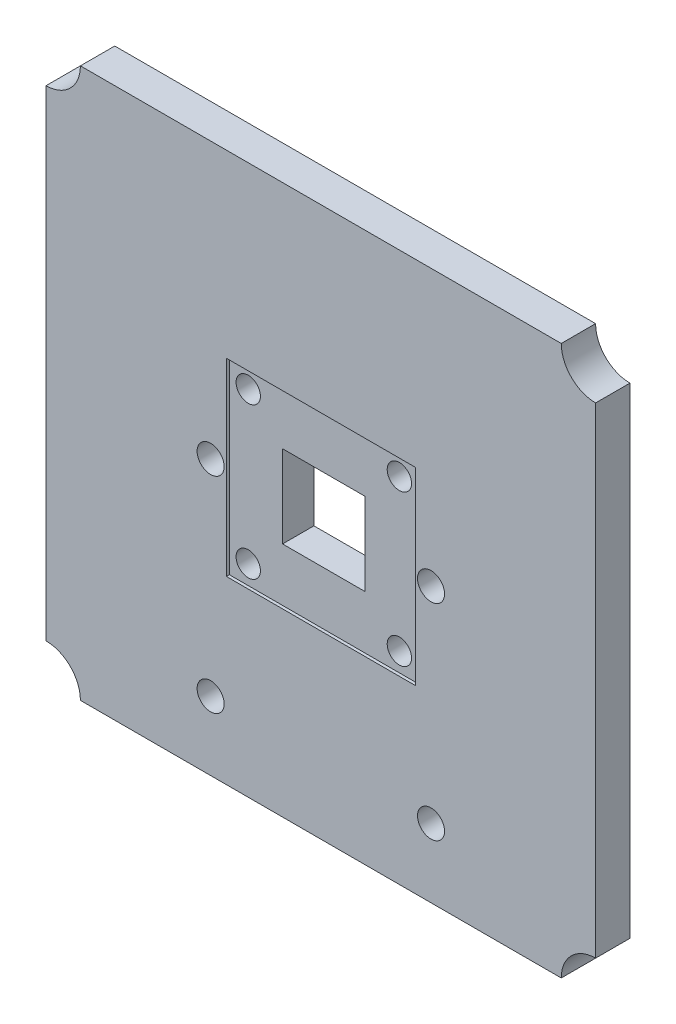
SolidWorks part; units mm, degrees
ref_plane "Front Plane" through (0, 0, 0) normal (0, 0, 1) x (1, 0, 0)
ref_plane "Top Plane" through (0, 0, 0) normal (0, 1, 0) x (1, 0, 0)
ref_plane "Right Plane" through (0, 0, 0) normal (1, 0, 0) x (0, 0, -1)
sketch "Sketch1" plane through (0, 0, 0) normal (0, 1, 0) x (1, 0, 0)
  line L1 (-57.15, 57.15) -> (57.15, 57.15)
  line L2 (-57.15, 57.15) -> (-57.15, -57.15)
  line L3 (-57.15, -57.15) -> (57.15, -57.15)
  line L4 (57.15, 57.15) -> (57.15, -57.15)
  point P4 (0, 57.15)
  point P7 (-57.15, 0)
  dimension "D1" = 114.3
  dimension "D2" = 114.3
extrude "Boss-Extrude1" add sketch "Sketch1" along normal mid plane 107.95
sketch "Sketch2" plane through (0, 53.975, 0) normal (0, 1, 0) x (1, 0, 0)
  line L1 (-50.8, 50.8) -> (50.8, 50.8)
  line L2 (-50.8, 50.8) -> (-50.8, -50.8)
  line L3 (-50.8, -50.8) -> (50.8, -50.8)
  line L4 (50.8, 50.8) -> (50.8, -50.8)
  arc A0 (-50.8, 44.45) -> (-44.45, 50.8) centre (-50.8, 50.8) ccw
  arc A1 (44.45, 50.8) -> (50.8, 44.45) centre (50.8, 50.8) ccw
  arc A2 (-50.8, -44.45) -> (-44.45, -50.8) centre (-50.8, -50.8) cw
  arc A3 (44.45, -50.8) -> (50.8, -44.45) centre (50.8, -50.8) cw
  point P4 (0, 50.8)
  point P5 (50.8, 0)
  dimension "D3" = 6.35
  dimension "D4" = 6.35
  dimension "D5" = 6.35
  dimension "D6" = 6.35
  dimension "D1" = 101.6
  dimension "D2" = 101.6
extrude "Cut-Extrude1" cut sketch "Sketch2" against normal blind 101.6 contours L3 A3 L4 A1 L1 A0 L2 A2 region at (0, 53.975, 0)
sketch "Sketch5" plane through (0, 0, -50.8) normal (0, 0, 1) x (1, 0, 0)
  line L0 (7.625, 3.185) -> (-7.625, 3.185) construction
  line L1 (-17.47, 20.655) -> (17.47, 20.655)
  line L2 (-17.47, 20.655) -> (-17.47, -14.285)
  line L3 (-17.47, -14.285) -> (17.47, -14.285)
  line L4 (17.47, 20.655) -> (17.47, -14.285)
  line L5 (-7.625, 10.81) -> (7.625, 10.81)
  line L6 (-7.625, 10.81) -> (-7.625, -4.44)
  line L7 (-7.625, -4.44) -> (7.625, -4.44)
  line L8 (7.625, 10.81) -> (7.625, -4.44)
  line L10 (-57.15, 53.975) -> (-57.15, -53.975) construction
  line L11 (0, 10.81) -> (0, -4.44) construction
  line L12 (-44.45, -47.625) -> (44.45, -47.625) construction
  point P8 (0, 10.81)
  point P9 (0, 20.655)
  point P12 (17.47, 3.185)
  point P13 (7.625, 3.185)
  dimension "D1" = 34.94
  dimension "D2" = 15.25
  dimension "D3" = 15.25
  dimension "D4" = 34.94
  dimension "D5" = 39.68
  dimension "D6" = 33.34
extrude "Cut-Extrude5" cut sketch "Sketch5" against normal blind 0.55
extrude "Cut-Extrude6" cut sketch "Sketch5<3>" against normal up to next contours L8 L5 L6 L7 | L6 L5 region at (0, 3.185, -50.8)
sketch "Sketch5<3>" plane through (0, 0, -50.8) normal (0, 0, 1) x (1, 0, 0) same geometry as "Sketch5"
sketch "Sketch13" plane through (0, 0, -57.15) normal (0, 0, -1) x (-1, 0, 0)
  line L0 (-57.15, 53.975) -> (57.15, 53.975) construction
  line L1 (-57.15, 53.975) -> (-57.15, -53.975) construction
  line L2 (57.15, 53.975) -> (57.15, -53.975) construction
  line L3 (-14.2875, 27.94) -> (-14.2875, 22.86) construction
  line L4 (14.2875, 22.86) -> (14.2875, 27.94) construction
  line L5 (13.7875, 29.177) -> (13.7875, 21.623)
  line L6 (14.7875, 29.177) -> (14.7875, 21.623)
  line L7 (11.5934, 22.7059) -> (16.9816, 28.0941)
  line L8 (11.5934, 28.0941) -> (16.9816, 22.7059)
  circle A0 centre (-14.2875, 25.4) radius 2.54
  circle A1 centre (14.2875, 25.4) radius 2.54
  circle A2 centre (14.2875, 25.4) radius 3.81
  point P19 (13.7875, 25.4)
  point P20 (14.7875, 25.4)
  dimension "D1" = 5.08
  dimension "D2" = 5.08
  dimension "D7" = 7.62
  dimension "D3" = 28.575
  dimension "D4" = 28.575
  dimension "D5" = 42.8625
  dimension "D6" = 42.8625
  dimension "D8" = 1
  dimension "D9" = 0.5
  dimension "D10" = 45
  dimension "D11" = 45
extrude "Boss-Extrude2" add sketch "Sketch13" along normal blind 1.27 contours A0
ref_plane "Plane1" through (14.2875, 25.4, -57.15) normal (0, -1, 0) x (-1, 0, 0)
sketch "Sketch14" plane through (14.2875, 25.4, -57.15) normal (0, -1, 0) x (-1, 0, 0)
  line L0 (0, 1.27) -> (0, 2.54)
  line L1 (2.54, 1.27) -> (-2.54, 1.27) construction
  line L2 (0, 2.54) -> (2.286, 2.54)
  line L3 (2.286, 2.54) -> (2.64, 1.905)
  line L4 (2.64, 1.905) -> (2.64, 1.27)
  line L5 (2.64, 1.27) -> (2.54, 1.27)
  line L6 (2.54, 0) -> (2.54, 1.27) construction
  line L7 (2.54, 1.27) -> (0, 1.27)
  dimension "D1" = 1.27
  dimension "D2" = 0.1
  dimension "D3" = 2.286
  dimension "D4" = 0.635
revolve "Revolve1" add sketch "Sketch14" angle 360 about L0
ref_plane "Plane2" through (-14.2875, 25.4, -57.15) normal (0, -1, 0) x (-1, 0, 0)
extrude "Cut-Extrude7" cut sketch "Sketch13<4>" against normal blind 2.54 contours L8 A1 L7 L6 | L6 A1 L8 | L5 A1 L6 L8 L7 | L7 A1 L6 | L6 A1 L5 L8 L7 | L7 L8 L6 | L8 L5 L7 | L8 A1 L7 L5 | L7 A1 L5 | L5 A1 L8 region at (-14.2875, 26.7822, -57.15) region at (-13.3374, 27.0404, -57.15) region at (-13.9542, 25.4, -57.15) region at (-12.7011, 25.4, -57.15) region at (-15.2376, 27.0404, -57.15) region at (-14.2875, 24.0178, -57.15) region at (-13.3374, 23.7596, -57.15) region at (-14.6208, 25.4, -57.15) region at (-15.8739, 25.4, -57.15) region at (-15.2376, 23.7596, -57.15)
sketch "Sketch13<4>" plane through (0, 0, -57.15) normal (0, 0, -1) x (-1, 0, 0) same geometry as "Sketch13"
extrude "Cut-Extrude8" cut sketch "Sketch13<5>" against normal blind 0.635 contours L7 A2 L5 A1 | L6 A2 L8 A1 | L7 A2 L6 A1 | L5 A2 L8 A1 region at (-12.8483, 28.2299, -57.15) region at (-15.7267, 28.2299, -57.15) region at (-12.8483, 22.5701, -57.15) region at (-15.7267, 22.5701, -57.15)
sketch "Sketch13<5>" plane through (0, 0, -57.15) normal (0, 0, -1) x (-1, 0, 0) same geometry as "Sketch13"
extrude "Cut-Extrude9" cut sketch "Sketch13<6>" against normal blind 1.27 contours L6 A2 L5 A1 | L5 A2 L6 A1 region at (-14.2875, 28.5612, -57.15) region at (-14.2875, 22.2388, -57.15)
sketch "Sketch13<6>" plane through (0, 0, -57.15) normal (0, 0, -1) x (-1, 0, 0) same geometry as "Sketch13"
sketch "Sketch17" plane through (-14.2875, 25.4, -57.15) normal (0, -1, 0) x (-1, 0, 0)
  line L0 (0, -1.27) -> (0, -2.54)
  line L1 (0.5, -1.27) -> (-0.5, -1.27) construction
  line L2 (0, -2.54) -> (2.286, -2.54)
  line L3 (2.286, -2.54) -> (2.64, -1.905)
  line L7 (2.54, -1.27) -> (0, -1.27)
  line L8 (2.64, -1.905) -> (2.64, -1.27)
  line L9 (2.64, -1.27) -> (2.54, -1.27)
  dimension "D1" = 2.54
  dimension "D2" = 2.286
  dimension "D3" = 0.1
  dimension "D4" = 1.27
  dimension "D5" = 0.635
revolve "Cut-Revolve1" cut sketch "Sketch17" angle 360 about L0
ref_plane "Plane3" through (0, 3.185, 0) normal (0, -1, 0) x (0, 0, 1)
ref_axis "Axis1" through (0, 3.185, 62.865) along (0, 0, -1)
ref_axis "Axis2" through (0, 59.3725, 0) along (0, -1, 0)
sketch "Sketch20" plane through (0, 0, -57.15) normal (0, 0, -1) x (-1, 0, 0)
  line L1 (-13.97, 17.155) -> (13.97, 17.155)
  line L2 (-13.97, 17.155) -> (-13.97, -10.785)
  line L3 (-13.97, -10.785) -> (13.97, -10.785)
  line L4 (13.97, 17.155) -> (13.97, -10.785)
  point P4 (0, 17.155)
  point P9 (13.97, 3.185)
  dimension "D1" = 27.94
  dimension "D2" = 27.94
hole_wizard "CBORE for M5 Hex Head Bolt2" positions "3DSketch4" profile "Sketch21" counterbore size "M5" standard "ANSI Metric"
sketch3d "3DSketch4"
  point P0 (13.97, 17.155, -57.15)
  point P3 (-13.97, 17.155, -57.15)
  point P6 (-13.97, -10.785, -57.15)
  point P9 (13.97, -10.785, -57.15)
sketch "Sketch21" plane through (13.97, 17.155, -57.15) normal (1, 0, 0) x (0, 1, 0)
  line L0 (0, 0) -> (0, 18.288)
  line L1 (0, 18.288) -> (2.75, 16.6356)
  line L2 (2.75, 16.6356) -> (2.75, 5.8)
  line L3 (2.75, 5.8) -> (2.25, 5.8)
  line L4 (2.25, 5.8) -> (2.25, 0)
  line L5 (2.25, 0) -> (0, 0)
  line L10 (0, 18.288) -> (-2.75, 16.6356) construction
  line L11 (0, -6.35) -> (0, 107.95) construction
  dimension "Hole Dia." = 5.5
  dimension "Hole Depth" = 18.288
  dimension "C'Bore Dia." = 4.5
  dimension "C'Bore Depth" = 5.8
  dimension "Drill Angle" = 118
sketch "Sketch23" plane through (0, 0, -59.69) normal (0, 0, -1) x (-1, 0, 0)
  line L0 (-14.7875, 27.9922) -> (-14.7875, 22.8078)
  line L1 (-13.7875, 27.9922) -> (-13.7875, 22.8078)
  line L2 (-14.2875, 28.04) -> (-14.2875, 22.76) construction
  circle A0 centre (-14.2875, 25.4) radius 2.64 construction
  circle A1 centre (-14.2875, 25.4) radius 2.64
  circle M1 centre (-14.2875, 25.4) radius 2.286
  dimension "D1" = 5.28
  dimension "D2" = 0.5
  dimension "D3" = 0.5
extrude "Cut-Extrude10" cut sketch "Sketch23" against normal blind 2.032 contours L2 L0 M1 | L2 L1 M1 | L2 A1 L0 M1 | A1 L2 L1 M1 | L2 A1 L1 M1 | L2 L0 A1 M1 region at (14.5384, 27.8458, -59.69) region at (14.5365, 25.4, -59.69) region at (14.0366, 27.8458, -59.69) region at (14.5384, 22.9542, -59.69) region at (14.0385, 25.4, -59.69) region at (14.0366, 22.9542, -59.69)
pattern_circular "CirPattern1" count 4 every 90 about axis through (0, 3.185, 62.865) along (0, 0, -1) of "Boss-Extrude2", "Revolve1", "Cut-Extrude7", "Cut-Extrude8", "Cut-Extrude9", "Cut-Revolve1", "Cut-Extrude10"
sketch "Sketch26" plane through (0, 0, 57.15) normal (0, 0, 1) x (1, 0, 0)
  line L1 (-57.15, 53.975) -> (57.15, 53.975)
  line L2 (-57.15, 53.975) -> (-57.15, -53.975)
  line L3 (-57.15, -53.975) -> (57.15, -53.975)
  line L4 (57.15, 53.975) -> (57.15, -53.975)
extrude "Cut-Extrude11" cut sketch "Sketch26" against normal blind 107.95
sketch "Sketch27" plane through (0, 0, -57.15) normal (0, 0, -1) x (-1, 0, 0)
  line L0 (-20.375, -34.925) -> (-20.375, 3.075) construction
  line L1 (-20.375, 3.075) -> (20.375, 3.075) construction
  line L2 (20.375, 3.075) -> (20.375, -34.925) construction
  line L3 (20.375, -34.925) -> (-20.375, -34.925) construction
  line L4 (-57.15, -53.975) -> (57.15, -53.975) construction
  circle A0 centre (-20.375, 3.075) radius 2.5
  circle A1 centre (20.375, 3.075) radius 2.5
  circle A2 centre (20.375, -34.925) radius 2.5
  circle A3 centre (-20.375, -34.925) radius 2.5
  point P8 (0, 3.075)
  point P9 (0, -34.925)
  dimension "D4" = 5
  dimension "D5" = 5
  dimension "D6" = 5
  dimension "D7" = 5
  dimension "D1" = 38
  dimension "D2" = 40.75
  dimension "D3" = 19.05
extrude "Cut-Extrude12" cut sketch "Sketch27" against normal up to next
sketch "Sketch29" plane through (0, 0, -57.15) normal (0, 0, -1) x (-1, 0, 0)
  line L0 (-57.15, 53.975) -> (57.15, 53.975) construction
  line L1 (-50.8, 53.975) -> (50.8, 53.975)
  line L2 (-50.8, 53.975) -> (-50.8, -47.625)
  line L3 (-50.8, -47.625) -> (50.8, -47.625)
  line L4 (50.8, 53.975) -> (50.8, -47.625)
  line L5 (-57.15, 53.975) -> (-57.15, -53.975) construction
  line L7 (-57.15, -53.975) -> (57.15, -53.975) construction
  line L9 (-57.15, 53.975) -> (57.15, 53.975)
  line L10 (-57.15, 53.975) -> (-57.15, -53.975)
  line L11 (-57.15, -53.975) -> (57.15, -53.975)
  line L12 (57.15, 53.975) -> (57.15, -53.975)
  circle A0 centre (-50.8, 53.975) radius 6.35
  circle A1 centre (50.8, 53.975) radius 6.35
  circle A2 centre (50.8, -47.625) radius 6.35
  circle A3 centre (-50.8, -47.625) radius 6.35
  point P6 (0, 53.975)
  dimension "D3" = 12.7
  dimension "D4" = 12.7
  dimension "D5" = 12.7
  dimension "D6" = 12.7
  dimension "D1" = 6.35
  dimension "D2" = 6.35
extrude "Cut-Extrude13" cut sketch "Sketch29" against normal blind 6.35 contours A3 L2 A0 L10 | L9 A0 L2 | L2 A0 L1 | L2 A3 L3 | L3 A3 L2 | A3 L10 L11 | A2 L11 L12 | A3 L11 A2 L3 | A2 L4 L3 | L4 A2 L3 | A2 L12 A1 L4 | L4 A1 L9 | L1 A1 L4 region at (48.105, 51.28, -57.15) region at (53.495, 51.28, -57.15) region at (54.0273, 3.175, -57.15) region at (-48.105, 51.28, -57.15) region at (48.105, -44.93, -57.15) region at (51.6983, -48.5233, -57.15) region at (55.7316, -52.5566, -57.15) region at (-53.495, 51.28, -57.15) region at (-54.0273, 3.175, -57.15) region at (0, -50.8523, -57.15) region at (-51.6983, -48.5233, -57.15) region at (-55.7316, -52.5566, -57.15) region at (-48.105, -44.93, -57.15)
